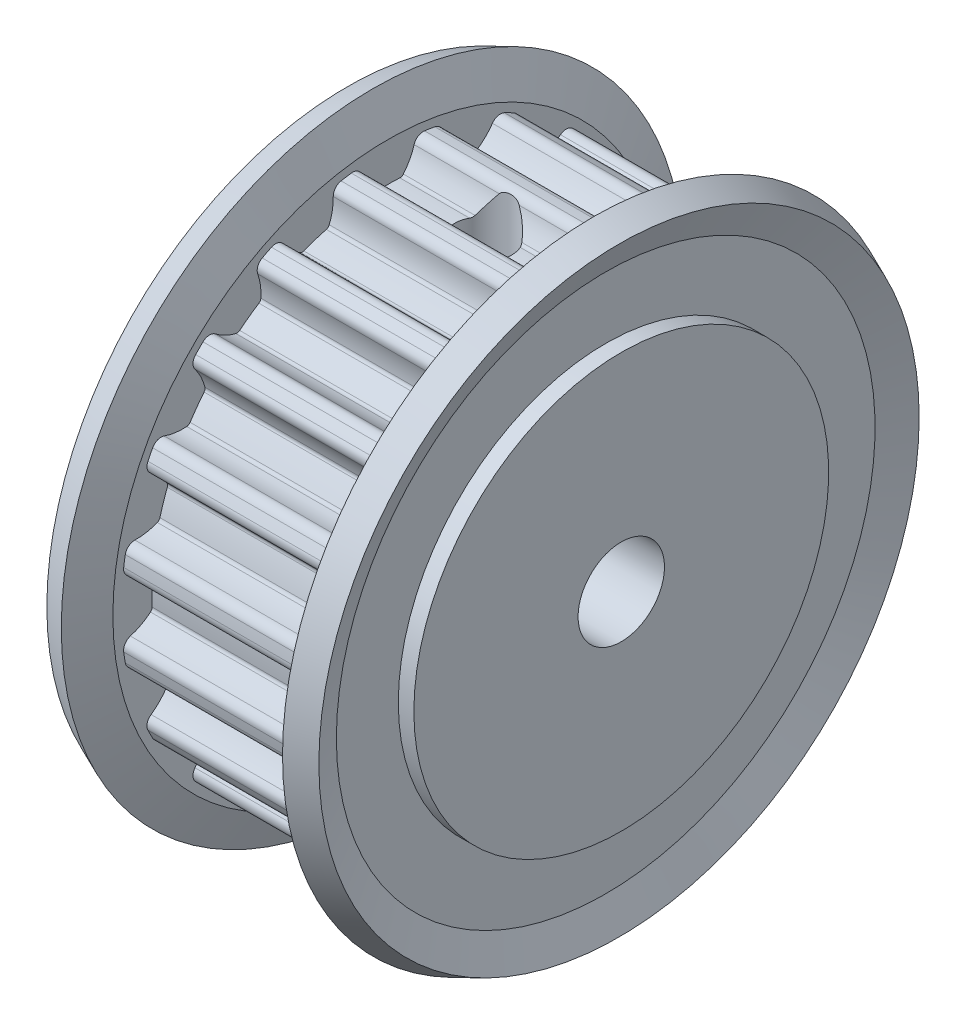
SolidWorks part; units mm, degrees
ref_plane "前视基准面" through (0, 0, 0) normal (0, 0, 1) x (1, 0, 0)
ref_plane "上视基准面" through (0, 0, 0) normal (0, 1, 0) x (1, 0, 0)
ref_plane "右视基准面" through (0, 0, 0) normal (1, 0, 0) x (0, 0, -1)
sketch "草图1" plane through (0, 0, 0) normal (0, 0, 1) x (1, 0, 0)
  line L0 (0, 12) -> (0, 2.5)
  line L1 (0, 2.5) -> (28, 2.5)
  line L2 (28, 2.5) -> (28, 4.175)
  line L3 (28, 4.175) -> (16, 4.175)
  line L4 (16, 4.175) -> (16, 12)
  line L5 (16, 12) -> (15.1, 12)
  line L6 (15.1, 12) -> (15.1, 15.5844)
  line L7 (15.1, 15.5844) -> (15.869, 17.3659)
  line L8 (15.869, 17.3659) -> (14.4, 18)
  line L9 (14.4, 18) -> (13.5, 15.915)
  line L10 (13.5, 15.915) -> (13.5, 15.435)
  line L11 (13.5, 15.435) -> (2.5, 15.435)
  line L12 (2.5, 15.435) -> (2.5, 15.915)
  line L13 (2.5, 15.915) -> (1.6, 18)
  line L14 (1.6, 18) -> (0.131, 17.3659)
  line L15 (0.131, 17.3659) -> (0.9, 15.5844)
  line L16 (0.9, 15.5844) -> (0.9, 12)
  line L17 (0.9, 12) -> (0, 12)
  line L18 (28, 0) -> (0, 0) construction
  dimension "D1" = 2.5
  dimension "D2" = 9.5
revolve "旋转1" add sketch "草图1" angle 360 about L18 reverse direction yes
sketch "草图2" plane through (0, 0, 0) normal (0, 0, 1) x (1, 0, 0)
  line L0 (16, 0) -> (16, 18)
  line L1 (16, 18) -> (32, 18)
  line L2 (32, 18) -> (32, 0)
  line L3 (32, 0) -> (16, 0)
  line L4 (32, 0) -> (16, 0) construction
revolve "切除-旋转1" cut sketch "草图2" angle 360 about L4 reverse direction yes
ref_plane "基准面1" through (2.5, 0, 0) normal (1, 0, 0) x (0, 0, -1)
sketch "草图3" plane through (2.5, 0, 0) normal (1, 0, 0) x (0, 0, -1)
  line L0 (2.1176, 15.2891) -> (2.1176, 20.58)
  line L1 (2.1176, 20.58) -> (-2.1176, 20.58)
  line L2 (-2.1176, 20.58) -> (-2.1176, 15.2891)
  arc A0 (-2.1176, 15.2891) -> (-1.5148, 14.9006) centre (-2.0421, 14.7443) cw
  arc A1 (-1.5148, 14.9006) -> (-0.8928, 13.7375) centre (1.625, 15.8318) ccw
  arc A2 (-0.8928, 13.7375) -> (-0.688, 13.6477) centre (-0.7006, 13.8974) ccw
  arc A3 (-0.688, 13.6477) -> (0.688, 13.6477) centre (0, 0) cw
  arc A4 (0.688, 13.6477) -> (0.8928, 13.7375) centre (0.7006, 13.8974) ccw
  arc A5 (0.8928, 13.7375) -> (1.5148, 14.9006) centre (-1.625, 15.8318) ccw
  arc A6 (1.5148, 14.9006) -> (2.1176, 15.2891) centre (2.0421, 14.7443) cw
extrude "切除-拉伸1" cut sketch "草图3" along normal blind 11
sketch "草图5" plane through (2.5, 0, 0) normal (1, 0, 0) x (0, 0, -1)
  line L0 (-2.7106, 15.1951) -> (-4.3456, 20.2271)
  line L1 (-4.3456, 20.2271) -> (-8.3735, 18.9184)
  line L2 (-8.3735, 18.9184) -> (-6.7385, 13.8864)
  arc A0 (-6.7385, 13.8864) -> (-6.0452, 13.7032) centre (-6.4984, 13.3916) cw
  arc A1 (-6.0452, 13.7032) -> (-5.0942, 12.7892) centre (-3.3468, 15.5591) ccw
  arc A2 (-5.0942, 12.7892) -> (-4.8717, 12.7671) centre (-4.9608, 13.0007) ccw
  arc A3 (-4.8717, 12.7671) -> (-3.563, 13.1923) centre (0, 0) cw
  arc A4 (-3.563, 13.1923) -> (-3.396, 13.341) centre (-3.6282, 13.4337) ccw
  arc A5 (-3.396, 13.341) -> (-3.1639, 14.6395) centre (-6.4378, 14.5548) ccw
  arc A6 (-3.1639, 14.6395) -> (-2.7106, 15.1951) centre (-2.614, 14.6537) cw
sketch "草图6" plane through (2.5, 0, 0) normal (1, 0, 0) x (0, 0, -1)
  line L0 (-7.2735, 13.6138) -> (-10.3835, 17.8943)
  line L1 (-10.3835, 17.8943) -> (-13.8098, 15.4049)
  line L2 (-13.8098, 15.4049) -> (-10.6998, 11.1244)
  arc A0 (-10.6998, 11.1244) -> (-9.9839, 11.1645) centre (-10.3186, 10.728) cw
  arc A1 (-9.9839, 11.1645) -> (-8.797, 10.5891) centre (-7.9911, 13.7634) ccw
  arc A2 (-8.797, 10.5891) -> (-8.5785, 10.6368) centre (-8.7355, 10.8314) ccw
  arc A3 (-8.5785, 10.6368) -> (-7.4653, 11.4456) centre (0, 0) cw
  arc A4 (-7.4653, 11.4456) -> (-7.3524, 11.6386) centre (-7.6019, 11.655) ccw
  arc A5 (-7.3524, 11.6386) -> (-7.5329, 12.9453) centre (-10.6204, 11.8531) ccw
  arc A6 (-7.5329, 12.9453) -> (-7.2735, 13.6138) centre (-7.0143, 13.1287) cw
sketch "草图7" plane through (2.5, 0, 0) normal (1, 0, 0) x (0, 0, -1)
  line L0 (-11.1244, 10.6998) -> (-15.4049, 13.8098)
  line L1 (-15.4049, 13.8098) -> (-17.8943, 10.3835)
  line L2 (-17.8943, 10.3835) -> (-13.6138, 7.2735)
  arc A0 (-13.6138, 7.2735) -> (-12.9453, 7.5329) centre (-13.1287, 7.0143) cw
  arc A1 (-12.9453, 7.5329) -> (-11.6386, 7.3524) centre (-11.8531, 10.6204) ccw
  arc A2 (-11.6386, 7.3524) -> (-11.4456, 7.4653) centre (-11.655, 7.6019) ccw
  arc A3 (-11.4456, 7.4653) -> (-10.6368, 8.5785) centre (0, 0) cw
  arc A4 (-10.6368, 8.5785) -> (-10.5891, 8.797) centre (-10.8314, 8.7355) ccw
  arc A5 (-10.5891, 8.797) -> (-11.1645, 9.9839) centre (-13.7634, 7.9911) ccw
  arc A6 (-11.1645, 9.9839) -> (-11.1244, 10.6998) centre (-10.728, 10.3186) cw
sketch "草图8" plane through (2.5, 0, 0) normal (1, 0, 0) x (0, 0, -1)
  line L0 (-13.8864, 6.7385) -> (-18.9184, 8.3735)
  line L1 (-18.9184, 8.3735) -> (-20.2271, 4.3456)
  line L2 (-20.2271, 4.3456) -> (-15.1951, 2.7106)
  arc A0 (-15.1951, 2.7106) -> (-14.6395, 3.1639) centre (-14.6537, 2.614) cw
  arc A1 (-14.6395, 3.1639) -> (-13.341, 3.396) centre (-14.5548, 6.4378) ccw
  arc A2 (-13.341, 3.396) -> (-13.1923, 3.563) centre (-13.4337, 3.6282) ccw
  arc A3 (-13.1923, 3.563) -> (-12.7671, 4.8717) centre (0, 0) cw
  arc A4 (-12.7671, 4.8717) -> (-12.7892, 5.0942) centre (-13.0007, 4.9608) ccw
  arc A5 (-12.7892, 5.0942) -> (-13.7032, 6.0452) centre (-15.5591, 3.3468) ccw
  arc A6 (-13.7032, 6.0452) -> (-13.8864, 6.7385) centre (-13.3916, 6.4984) cw
sketch "草图9" plane through (2.5, 0, 0) normal (1, 0, 0) x (0, 0, -1)
  line L0 (-15.2891, 2.1176) -> (-20.58, 2.1176)
  line L1 (-20.58, 2.1176) -> (-20.58, -2.1176)
  line L2 (-20.58, -2.1176) -> (-15.2891, -2.1176)
  arc A0 (-15.2891, -2.1176) -> (-14.9006, -1.5148) centre (-14.7443, -2.0421) cw
  arc A1 (-14.9006, -1.5148) -> (-13.7375, -0.8928) centre (-15.8318, 1.625) ccw
  arc A2 (-13.7375, -0.8928) -> (-13.6477, -0.688) centre (-13.8974, -0.7006) ccw
  arc A3 (-13.6477, -0.688) -> (-13.6477, 0.688) centre (0, 0) cw
  arc A4 (-13.6477, 0.688) -> (-13.7375, 0.8928) centre (-13.8974, 0.7006) ccw
  arc A5 (-13.7375, 0.8928) -> (-14.9006, 1.5148) centre (-15.8318, -1.625) ccw
  arc A6 (-14.9006, 1.5148) -> (-15.2891, 2.1176) centre (-14.7443, 2.0421) cw
sketch "草图10" plane through (2.5, 0, 0) normal (1, 0, 0) x (0, 0, -1)
  line L0 (-15.1951, -2.7106) -> (-20.2271, -4.3456)
  line L1 (-20.2271, -4.3456) -> (-18.9184, -8.3735)
  line L2 (-18.9184, -8.3735) -> (-13.8864, -6.7385)
  arc A0 (-13.8864, -6.7385) -> (-13.7032, -6.0452) centre (-13.3916, -6.4984) cw
  arc A1 (-13.7032, -6.0452) -> (-12.7892, -5.0942) centre (-15.5591, -3.3468) ccw
  arc A2 (-12.7892, -5.0942) -> (-12.7671, -4.8717) centre (-13.0007, -4.9608) ccw
  arc A3 (-12.7671, -4.8717) -> (-13.1923, -3.563) centre (0, 0) cw
  arc A4 (-13.1923, -3.563) -> (-13.341, -3.396) centre (-13.4337, -3.6282) ccw
  arc A5 (-13.341, -3.396) -> (-14.6395, -3.1639) centre (-14.5548, -6.4378) ccw
  arc A6 (-14.6395, -3.1639) -> (-15.1951, -2.7106) centre (-14.6537, -2.614) cw
sketch "草图11" plane through (2.5, 0, 0) normal (1, 0, 0) x (0, 0, -1)
  line L0 (-13.6138, -7.2735) -> (-17.8943, -10.3835)
  line L1 (-17.8943, -10.3835) -> (-15.4049, -13.8098)
  line L2 (-15.4049, -13.8098) -> (-11.1244, -10.6998)
  arc A0 (-11.1244, -10.6998) -> (-11.1645, -9.9839) centre (-10.728, -10.3186) cw
  arc A1 (-11.1645, -9.9839) -> (-10.5891, -8.797) centre (-13.7634, -7.9911) ccw
  arc A2 (-10.5891, -8.797) -> (-10.6368, -8.5785) centre (-10.8314, -8.7355) ccw
  arc A3 (-10.6368, -8.5785) -> (-11.4456, -7.4653) centre (0, 0) cw
  arc A4 (-11.4456, -7.4653) -> (-11.6386, -7.3524) centre (-11.655, -7.6019) ccw
  arc A5 (-11.6386, -7.3524) -> (-12.9453, -7.5329) centre (-11.8531, -10.6204) ccw
  arc A6 (-12.9453, -7.5329) -> (-13.6138, -7.2735) centre (-13.1287, -7.0143) cw
sketch "草图12" plane through (2.5, 0, 0) normal (1, 0, 0) x (0, 0, -1)
  line L0 (-10.6998, -11.1244) -> (-13.8098, -15.4049)
  line L1 (-13.8098, -15.4049) -> (-10.3835, -17.8943)
  line L2 (-10.3835, -17.8943) -> (-7.2735, -13.6138)
  arc A0 (-7.2735, -13.6138) -> (-7.5329, -12.9453) centre (-7.0143, -13.1287) cw
  arc A1 (-7.5329, -12.9453) -> (-7.3524, -11.6386) centre (-10.6204, -11.8531) ccw
  arc A2 (-7.3524, -11.6386) -> (-7.4653, -11.4456) centre (-7.6019, -11.655) ccw
  arc A3 (-7.4653, -11.4456) -> (-8.5785, -10.6368) centre (0, 0) cw
  arc A4 (-8.5785, -10.6368) -> (-8.797, -10.5891) centre (-8.7355, -10.8314) ccw
  arc A5 (-8.797, -10.5891) -> (-9.9839, -11.1645) centre (-7.9911, -13.7634) ccw
  arc A6 (-9.9839, -11.1645) -> (-10.6998, -11.1244) centre (-10.3186, -10.728) cw
sketch "草图13" plane through (2.5, 0, 0) normal (1, 0, 0) x (0, 0, -1)
  line L0 (-6.7385, -13.8864) -> (-8.3735, -18.9184)
  line L1 (-8.3735, -18.9184) -> (-4.3456, -20.2271)
  line L2 (-4.3456, -20.2271) -> (-2.7106, -15.1951)
  arc A0 (-2.7106, -15.1951) -> (-3.1639, -14.6395) centre (-2.614, -14.6537) cw
  arc A1 (-3.1639, -14.6395) -> (-3.396, -13.341) centre (-6.4378, -14.5548) ccw
  arc A2 (-3.396, -13.341) -> (-3.563, -13.1923) centre (-3.6282, -13.4337) ccw
  arc A3 (-3.563, -13.1923) -> (-4.8717, -12.7671) centre (0, 0) cw
  arc A4 (-4.8717, -12.7671) -> (-5.0942, -12.7892) centre (-4.9608, -13.0007) ccw
  arc A5 (-5.0942, -12.7892) -> (-6.0452, -13.7032) centre (-3.3468, -15.5591) ccw
  arc A6 (-6.0452, -13.7032) -> (-6.7385, -13.8864) centre (-6.4984, -13.3916) cw
sketch "草图14" plane through (2.5, 0, 0) normal (1, 0, 0) x (0, 0, -1)
  line L0 (-2.1176, -15.2891) -> (-2.1176, -20.58)
  line L1 (-2.1176, -20.58) -> (2.1176, -20.58)
  line L2 (2.1176, -20.58) -> (2.1176, -15.2891)
  arc A0 (2.1176, -15.2891) -> (1.5148, -14.9006) centre (2.0421, -14.7443) cw
  arc A1 (1.5148, -14.9006) -> (0.8928, -13.7375) centre (-1.625, -15.8318) ccw
  arc A2 (0.8928, -13.7375) -> (0.688, -13.6477) centre (0.7006, -13.8974) ccw
  arc A3 (0.688, -13.6477) -> (-0.688, -13.6477) centre (0, 0) cw
  arc A4 (-0.688, -13.6477) -> (-0.8928, -13.7375) centre (-0.7006, -13.8974) ccw
  arc A5 (-0.8928, -13.7375) -> (-1.5148, -14.9006) centre (1.625, -15.8318) ccw
  arc A6 (-1.5148, -14.9006) -> (-2.1176, -15.2891) centre (-2.0421, -14.7443) cw
sketch "草图15" plane through (2.5, 0, 0) normal (1, 0, 0) x (0, 0, -1)
  line L0 (2.7106, -15.1951) -> (4.3456, -20.2271)
  line L1 (4.3456, -20.2271) -> (8.3735, -18.9184)
  line L2 (8.3735, -18.9184) -> (6.7385, -13.8864)
  arc A0 (6.7385, -13.8864) -> (6.0452, -13.7032) centre (6.4984, -13.3916) cw
  arc A1 (6.0452, -13.7032) -> (5.0942, -12.7892) centre (3.3468, -15.5591) ccw
  arc A2 (5.0942, -12.7892) -> (4.8717, -12.7671) centre (4.9608, -13.0007) ccw
  arc A3 (4.8717, -12.7671) -> (3.563, -13.1923) centre (0, 0) cw
  arc A4 (3.563, -13.1923) -> (3.396, -13.341) centre (3.6282, -13.4337) ccw
  arc A5 (3.396, -13.341) -> (3.1639, -14.6395) centre (6.4378, -14.5548) ccw
  arc A6 (3.1639, -14.6395) -> (2.7106, -15.1951) centre (2.614, -14.6537) cw
sketch "草图16" plane through (2.5, 0, 0) normal (1, 0, 0) x (0, 0, -1)
  line L0 (7.2735, -13.6138) -> (10.3835, -17.8943)
  line L1 (10.3835, -17.8943) -> (13.8098, -15.4049)
  line L2 (13.8098, -15.4049) -> (10.6998, -11.1244)
  arc A0 (10.6998, -11.1244) -> (9.9839, -11.1645) centre (10.3186, -10.728) cw
  arc A1 (9.9839, -11.1645) -> (8.797, -10.5891) centre (7.9911, -13.7634) ccw
  arc A2 (8.797, -10.5891) -> (8.5785, -10.6368) centre (8.7355, -10.8314) ccw
  arc A3 (8.5785, -10.6368) -> (7.4653, -11.4456) centre (0, 0) cw
  arc A4 (7.4653, -11.4456) -> (7.3524, -11.6386) centre (7.6019, -11.655) ccw
  arc A5 (7.3524, -11.6386) -> (7.5329, -12.9453) centre (10.6204, -11.8531) ccw
  arc A6 (7.5329, -12.9453) -> (7.2735, -13.6138) centre (7.0143, -13.1287) cw
sketch "草图17" plane through (2.5, 0, 0) normal (1, 0, 0) x (0, 0, -1)
  line L0 (11.1244, -10.6998) -> (15.4049, -13.8098)
  line L1 (15.4049, -13.8098) -> (17.8943, -10.3835)
  line L2 (17.8943, -10.3835) -> (13.6138, -7.2735)
  arc A0 (13.6138, -7.2735) -> (12.9453, -7.5329) centre (13.1287, -7.0143) cw
  arc A1 (12.9453, -7.5329) -> (11.6386, -7.3524) centre (11.8531, -10.6204) ccw
  arc A2 (11.6386, -7.3524) -> (11.4456, -7.4653) centre (11.655, -7.6019) ccw
  arc A3 (11.4456, -7.4653) -> (10.6368, -8.5785) centre (0, 0) cw
  arc A4 (10.6368, -8.5785) -> (10.5891, -8.797) centre (10.8314, -8.7355) ccw
  arc A5 (10.5891, -8.797) -> (11.1645, -9.9839) centre (13.7634, -7.9911) ccw
  arc A6 (11.1645, -9.9839) -> (11.1244, -10.6998) centre (10.728, -10.3186) cw
sketch "草图18" plane through (2.5, 0, 0) normal (1, 0, 0) x (0, 0, -1)
  line L0 (13.8864, -6.7385) -> (18.9184, -8.3735)
  line L1 (18.9184, -8.3735) -> (20.2271, -4.3456)
  line L2 (20.2271, -4.3456) -> (15.1951, -2.7106)
  arc A0 (15.1951, -2.7106) -> (14.6395, -3.1639) centre (14.6537, -2.614) cw
  arc A1 (14.6395, -3.1639) -> (13.341, -3.396) centre (14.5548, -6.4378) ccw
  arc A2 (13.341, -3.396) -> (13.1923, -3.563) centre (13.4337, -3.6282) ccw
  arc A3 (13.1923, -3.563) -> (12.7671, -4.8717) centre (0, 0) cw
  arc A4 (12.7671, -4.8717) -> (12.7892, -5.0942) centre (13.0007, -4.9608) ccw
  arc A5 (12.7892, -5.0942) -> (13.7032, -6.0452) centre (15.5591, -3.3468) ccw
  arc A6 (13.7032, -6.0452) -> (13.8864, -6.7385) centre (13.3916, -6.4984) cw
sketch "草图19" plane through (2.5, 0, 0) normal (1, 0, 0) x (0, 0, -1)
  line L0 (15.2891, -2.1176) -> (20.58, -2.1176)
  line L1 (20.58, -2.1176) -> (20.58, 2.1176)
  line L2 (20.58, 2.1176) -> (15.2891, 2.1176)
  arc A0 (15.2891, 2.1176) -> (14.9006, 1.5148) centre (14.7443, 2.0421) cw
  arc A1 (14.9006, 1.5148) -> (13.7375, 0.8928) centre (15.8318, -1.625) ccw
  arc A2 (13.7375, 0.8928) -> (13.6477, 0.688) centre (13.8974, 0.7006) ccw
  arc A3 (13.6477, 0.688) -> (13.6477, -0.688) centre (0, 0) cw
  arc A4 (13.6477, -0.688) -> (13.7375, -0.8928) centre (13.8974, -0.7006) ccw
  arc A5 (13.7375, -0.8928) -> (14.9006, -1.5148) centre (15.8318, 1.625) ccw
  arc A6 (14.9006, -1.5148) -> (15.2891, -2.1176) centre (14.7443, -2.0421) cw
sketch "草图20" plane through (2.5, 0, 0) normal (1, 0, 0) x (0, 0, -1)
  line L0 (15.1951, 2.7106) -> (20.2271, 4.3456)
  line L1 (20.2271, 4.3456) -> (18.9184, 8.3735)
  line L2 (18.9184, 8.3735) -> (13.8864, 6.7385)
  arc A0 (13.8864, 6.7385) -> (13.7032, 6.0452) centre (13.3916, 6.4984) cw
  arc A1 (13.7032, 6.0452) -> (12.7892, 5.0942) centre (15.5591, 3.3468) ccw
  arc A2 (12.7892, 5.0942) -> (12.7671, 4.8717) centre (13.0007, 4.9608) ccw
  arc A3 (12.7671, 4.8717) -> (13.1923, 3.563) centre (0, 0) cw
  arc A4 (13.1923, 3.563) -> (13.341, 3.396) centre (13.4337, 3.6282) ccw
  arc A5 (13.341, 3.396) -> (14.6395, 3.1639) centre (14.5548, 6.4378) ccw
  arc A6 (14.6395, 3.1639) -> (15.1951, 2.7106) centre (14.6537, 2.614) cw
sketch "草图21" plane through (2.5, 0, 0) normal (1, 0, 0) x (0, 0, -1)
  line L0 (13.6138, 7.2735) -> (17.8943, 10.3835)
  line L1 (17.8943, 10.3835) -> (15.4049, 13.8098)
  line L2 (15.4049, 13.8098) -> (11.1244, 10.6998)
  arc A0 (11.1244, 10.6998) -> (11.1645, 9.9839) centre (10.728, 10.3186) cw
  arc A1 (11.1645, 9.9839) -> (10.5891, 8.797) centre (13.7634, 7.9911) ccw
  arc A2 (10.5891, 8.797) -> (10.6368, 8.5785) centre (10.8314, 8.7355) ccw
  arc A3 (10.6368, 8.5785) -> (11.4456, 7.4653) centre (0, 0) cw
  arc A4 (11.4456, 7.4653) -> (11.6386, 7.3524) centre (11.655, 7.6019) ccw
  arc A5 (11.6386, 7.3524) -> (12.9453, 7.5329) centre (11.8531, 10.6204) ccw
  arc A6 (12.9453, 7.5329) -> (13.6138, 7.2735) centre (13.1287, 7.0143) cw
sketch "草图22" plane through (2.5, 0, 0) normal (1, 0, 0) x (0, 0, -1)
  line L0 (10.6998, 11.1244) -> (13.8098, 15.4049)
  line L1 (13.8098, 15.4049) -> (10.3835, 17.8943)
  line L2 (10.3835, 17.8943) -> (7.2735, 13.6138)
  arc A0 (7.2735, 13.6138) -> (7.5329, 12.9453) centre (7.0143, 13.1287) cw
  arc A1 (7.5329, 12.9453) -> (7.3524, 11.6386) centre (10.6204, 11.8531) ccw
  arc A2 (7.3524, 11.6386) -> (7.4653, 11.4456) centre (7.6019, 11.655) ccw
  arc A3 (7.4653, 11.4456) -> (8.5785, 10.6368) centre (0, 0) cw
  arc A4 (8.5785, 10.6368) -> (8.797, 10.5891) centre (8.7355, 10.8314) ccw
  arc A5 (8.797, 10.5891) -> (9.9839, 11.1645) centre (7.9911, 13.7634) ccw
  arc A6 (9.9839, 11.1645) -> (10.6998, 11.1244) centre (10.3186, 10.728) cw
sketch "草图23" plane through (2.5, 0, 0) normal (1, 0, 0) x (0, 0, -1)
  line L0 (6.7385, 13.8864) -> (8.3735, 18.9184)
  line L1 (8.3735, 18.9184) -> (4.3456, 20.2271)
  line L2 (4.3456, 20.2271) -> (2.7106, 15.1951)
  arc A0 (2.7106, 15.1951) -> (3.1639, 14.6395) centre (2.614, 14.6537) cw
  arc A1 (3.1639, 14.6395) -> (3.396, 13.341) centre (6.4378, 14.5548) ccw
  arc A2 (3.396, 13.341) -> (3.563, 13.1923) centre (3.6282, 13.4337) ccw
  arc A3 (3.563, 13.1923) -> (4.8717, 12.7671) centre (0, 0) cw
  arc A4 (4.8717, 12.7671) -> (5.0942, 12.7892) centre (4.9608, 13.0007) ccw
  arc A5 (5.0942, 12.7892) -> (6.0452, 13.7032) centre (3.3468, 15.5591) ccw
  arc A6 (6.0452, 13.7032) -> (6.7385, 13.8864) centre (6.4984, 13.3916) cw
extrude "切除-拉伸2" cut sketch "草图5" along normal blind 11
extrude "切除-拉伸3" cut sketch "草图6" along normal blind 11
extrude "切除-拉伸4" cut sketch "草图7" along normal blind 11
extrude "切除-拉伸5" cut sketch "草图8" along normal blind 11
extrude "切除-拉伸6" cut sketch "草图9" along normal blind 11
extrude "切除-拉伸7" cut sketch "草图10" along normal blind 11
extrude "切除-拉伸8" cut sketch "草图11" along normal blind 11
extrude "切除-拉伸9" cut sketch "草图12" along normal blind 11
extrude "切除-拉伸10" cut sketch "草图13" along normal blind 11
extrude "切除-拉伸11" cut sketch "草图14" along normal blind 11
extrude "切除-拉伸12" cut sketch "草图15" along normal blind 11
extrude "切除-拉伸13" cut sketch "草图16" along normal blind 11
extrude "切除-拉伸14" cut sketch "草图17" along normal blind 11
extrude "切除-拉伸15" cut sketch "草图18" along normal blind 11
extrude "切除-拉伸16" cut sketch "草图19" along normal blind 11
extrude "切除-拉伸17" cut sketch "草图20" along normal blind 11
extrude "切除-拉伸18" cut sketch "草图21" along normal blind 11
extrude "切除-拉伸19" cut sketch "草图22" along normal blind 11
extrude "切除-拉伸20" cut sketch "草图23" along normal blind 11
ref_plane "基准面2" through (8, 0, 0) normal (1, 0, 0) x (0, 0, -1)
sketch "草图24" plane through (8, 0, 0) normal (1, 0, 0) x (0, 0, -1)
  line L0 (0, 15.435) -> (1.621, 15.435)
  line L1 (1.621, 15.435) -> (1.621, 2.675)
  line L2 (1.621, 2.675) -> (0, 2.675)
  line L3 (0, 2.675) -> (0, 15.435)
  line L4 (0, 2.675) -> (0, 15.435) construction
revolve "切除-旋转2" cut sketch "草图24" angle 360 about L4 reverse direction yes
sketch "草图25" plane through (8, 0, 0) normal (1, 0, 0) x (0, 0, -1)
  line L0 (12.4872, -9.0725) -> (11.5344, -10.3839)
  line L1 (11.5344, -10.3839) -> (-0.9528, -1.3114)
  line L2 (-0.9528, -1.3114) -> (0, 0)
  line L3 (0, 0) -> (12.4872, -9.0725)
  line L4 (0, 0) -> (12.4872, -9.0725) construction
revolve "切除-旋转3" cut sketch "草图25" angle 360 about L4 reverse direction yes
ref_plane "基准面3" through (0, 0, 0) normal (0, 0.866, 0.5) x (1, 0, 0)
ref_plane "基准面4" through (0, 0, 0) normal (0, -0.5, 0.866) x (1, 0, 0)
ref_plane "基准面5" through (16, 0, 0) normal (1, 0, 0) x (0, 0, -1)
ref_plane "基准面6" through (0, 0, 0) normal (0, 1, 0) x (1, 0, 0)
ref_plane "基准面7" through (0, 0, 0) normal (0, 0, -1) x (-1, 0, 0)
ref_plane "基准面8" through (0, 0, 0) normal (0, 1, 0) x (1, 0, 0)
ref_plane "基准面9" through (0, 15.435, 0) normal (0, 1, 0) x (1, 0, 0)
ref_plane "基准面10" through (0, 0, 0) normal (0, -0.5878, -0.809) x (-1, 0, 0)
ref_plane "基准面11" through (0, -9.0725, -12.4872) normal (0, -0.5878, -0.809) x (-1, 0, 0)
ref_plane "基准面12" through (8, 0, 0) normal (1, 0, 0) x (0, 0, -1)
ref_plane "to_s1 XY" through (0, 15.435, 0) normal (0, 1, 0) x (1, 0, 0)
ref_plane "to_s1 XZ" through (0, 0, 0) normal (0, 0, 1) x (1, 0, 0)
ref_plane "to_s1 YZ" through (8, 0, 0) normal (1, 0, 0) x (0, 0, -1)
ref_axis "to_s1 X" through (-80.9, 15.435, 0) along (1, 0, 0)
ref_axis "to_s1 Y" through (8, 15.435, 50) along (0, 0, -1)
ref_axis "to_s1 Z" through (8, 50, 0) along (0, -1, 0)
sketch3d "to_s1"
  point P0 (8, 15.435, 0)
ref_plane "to_s2 XY" through (0, -9.0725, -12.4872) normal (0, -0.5878, -0.809) x (-1, 0, 0)
ref_plane "to_s2 XZ" through (0, 0, 0) normal (0, 0.809, -0.5878) x (1, 0, 0)
ref_plane "to_s2 YZ" through (8, 0, 0) normal (1, 0, 0) x (0, 0, -1)
ref_axis "to_s2 X" through (-80.9, -9.0725, -12.4872) along (1, 0, 0)
ref_axis "to_s2 Y" through (8, 31.3784, -41.8764) along (0, -0.809, 0.5878)
ref_axis "to_s2 Z" through (8, -50, -68.8191) along (0, 0.5878, 0.809)
sketch3d "to_s2"
  point P0 (8, -9.0725, -12.4872)
ref_plane "C1 XY" through (8, 0, 0) normal (1, 0, 0) x (0, 0, -1)
ref_plane "C1 XZ" through (0, 0, 0) normal (0, -1, 0) x (-1, 0, 0)
ref_plane "C1 YZ" through (0, 0, 0) normal (0, 0, -1) x (-1, 0, 0)
ref_axis "C1 X" through (8, 0, 80.9) along (0, 0, -1)
ref_axis "C1 Y" through (8, -50, 0) along (0, 1, 0)
ref_axis "C1 Z" through (80.9, 0, 0) along (-1, 0, 0)
sketch3d "C1"
  point P0 (8, 0, 0)
